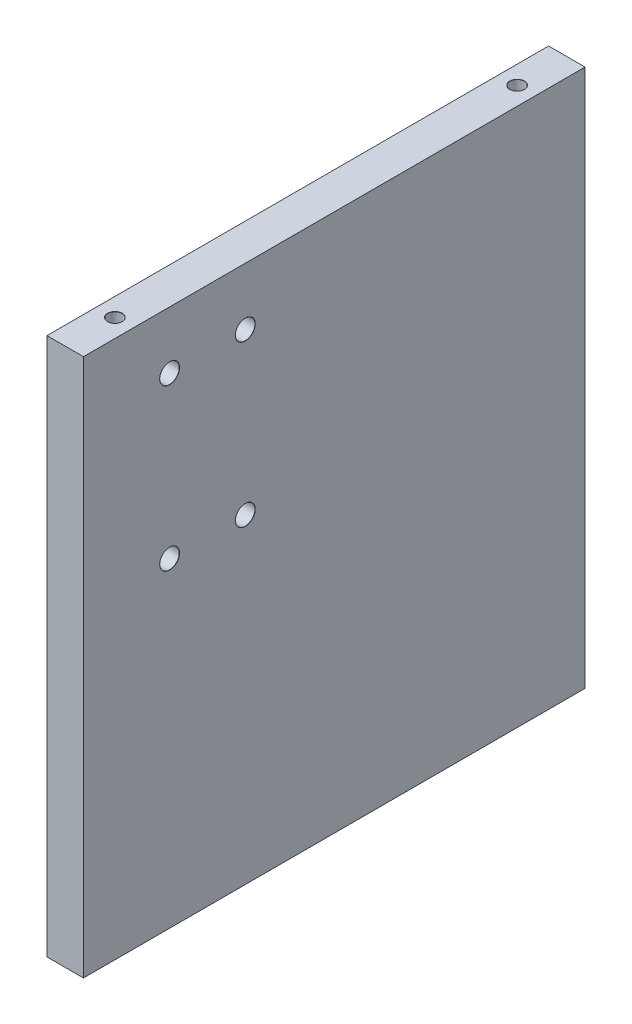
SolidWorks part; units mm, degrees
ref_plane "Front Plane" through (0, 0, 0) normal (0, 0, 1) x (1, 0, 0)
ref_plane "Top Plane" through (0, 0, 0) normal (0, 1, 0) x (1, 0, 0)
ref_plane "Right Plane" through (0, 0, 0) normal (1, 0, 0) x (0, 0, -1)
sketch "Sketch1" plane through (0, 0, 0) normal (1, 0, 0) x (0, 0, -1)
  line L1 (-43.65, -46.825) -> (43.65, -46.825)
  line L2 (-43.65, -46.825) -> (-43.65, 46.825)
  line L3 (-43.65, 46.825) -> (43.65, 46.825)
  line L4 (43.65, -46.825) -> (43.65, 46.825)
  line L5 (-43.65, -46.825) -> (43.65, 46.825) construction
  line L6 (-43.65, 46.825) -> (43.65, -46.825) construction
  point P0 (0, 0)
extrude "Boss-Extrude1" add sketch "Sketch1" along normal blind 6.35
sketch "Sketch2" plane through (0, 46.825, 0) normal (0, 1, 0) x (1, 0, 0)
  line L0 (3.175, 43.65) -> (3.175, 35)
  line L1 (6.35, 43.65) -> (0, 43.65) construction
  line L2 (3.175, -43.65) -> (3.175, -35)
  line L3 (6.35, -43.65) -> (0, -43.65) construction
hole_wizard "Tap Drill for M3x0.5 Tap1" positions "Sketch3" profile "Sketch4" hole size "M3x0.5" standard "ANSI Metric"
sketch "Sketch3" plane through (0, 46.825, 0) normal (0, 1, 0) x (1, 0, 0)
  point P0 (3.175, 35)
  point P3 (3.175, -35)
sketch "Sketch4" plane through (3.175, 46.825, -35) normal (1, 0, 0) x (0, 0, 1)
  line L0 (0, 0) -> (0, 10.7511)
  line L1 (0, 10.7511) -> (1.25, 10)
  line L2 (1.25, 10) -> (1.25, 0.025)
  line L3 (1.25, 0.025) -> (1.275, 0)
  line L5 (1.275, 0) -> (0, 0)
  line L6 (-1.25, 0.025) -> (-1.275, 0) construction
  line L10 (0, 10.7511) -> (-1.25, 10) construction
  line L11 (0, -6.35) -> (0, 107.95) construction
  dimension "Hole Dia." = 2.5
  dimension "Hole Depth" = 10
  dimension "Near C'Sink Dia." = 2.55
  dimension "Near C'Sink Angle" = 90
  dimension "Drill Angle" = 118
sketch "Sketch5" plane through (0, -46.825, 0) normal (0, -1, 0) x (1, 0, 0)
  line L0 (3.175, 43.65) -> (3.175, 35)
  line L1 (3.175, -43.65) -> (3.175, -35)
  line L2 (6.35, -43.65) -> (0, -43.65) construction
hole_wizard "Tap Drill for M3x0.5 Tap2" positions "Sketch6" profile "Sketch7" hole size "M3x0.5" standard "ANSI Metric"
sketch "Sketch6" plane through (0, -46.825, 0) normal (0, -1, 0) x (-1, 0, 0)
  point P0 (-3.175, -35)
  point P3 (-3.175, 35)
sketch "Sketch7" plane through (3.175, -46.825, 35) normal (1, 0, 0) x (0, 0, -1)
  line L0 (0, 0) -> (0, 10)
  line L1 (0, 10) -> (1.25, 9.2489)
  line L2 (1.25, 9.2489) -> (1.25, 0.025)
  line L3 (1.25, 0.025) -> (1.275, 0)
  line L5 (1.275, 0) -> (0, 0)
  line L6 (-1.25, 0.025) -> (-1.275, 0) construction
  line L10 (0, 10) -> (-1.25, 9.2489) construction
  line L11 (0, -6.35) -> (0, 107.95) construction
  dimension "Hole Dia." = 2.5
  dimension "Hole Depth" = 10
  dimension "Near C'Sink Dia." = 2.55
  dimension "Near C'Sink Angle" = 90
  dimension "Drill Angle" = 118
sketch "Sketch11" plane through (6.35, 0, 0) normal (1, 0, 0) x (0, 0, -1)
  line L0 (-43.65, 46.825) -> (-43.65, 36.825)
  line L1 (-43.65, 46.825) -> (-43.65, -46.825) construction
  line L2 (-43.65, 36.825) -> (-28.65, 36.825)
  line L3 (-28.65, 36.825) -> (-28.65, 8.885)
  line L4 (-28.65, 8.885) -> (-15.48, 8.885)
  line L5 (-15.48, 8.885) -> (-15.48, 36.825)
hole_wizard "M3 Clearance Hole2" positions "Sketch12" profile "Sketch13" hole size "M3" standard "ANSI Metric" end condition through all
sketch "Sketch12" plane through (6.35, 0, 0) normal (1, 0, 0) x (0, 0, -1)
  point P0 (-28.65, 36.825)
  point P3 (-15.48, 36.825)
  point P6 (-15.48, 8.885)
  point P9 (-28.65, 8.885)
sketch "Sketch13" plane through (6.35, 36.825, 28.65) normal (0, 1, 0) x (0, 0, -1)
  line L0 (0, 0) -> (0, 6.35)
  line L1 (0, 6.35) -> (1.7, 6.35)
  line L2 (1.7, 6.35) -> (1.7, 0.025)
  line L3 (1.7, 0.025) -> (1.725, 0)
  line L5 (1.725, 0) -> (0, 0)
  line L6 (-1.7, 0.025) -> (-1.725, 0) construction
  line L11 (0, -6.35) -> (0, 107.95) construction
  dimension "Thru Hole Dia." = 3.4
  dimension "Thru Hole Depth" = 6.35
  dimension "Near C'Sink Dia." = 3.45
  dimension "Near C'Sink Angle" = 90
